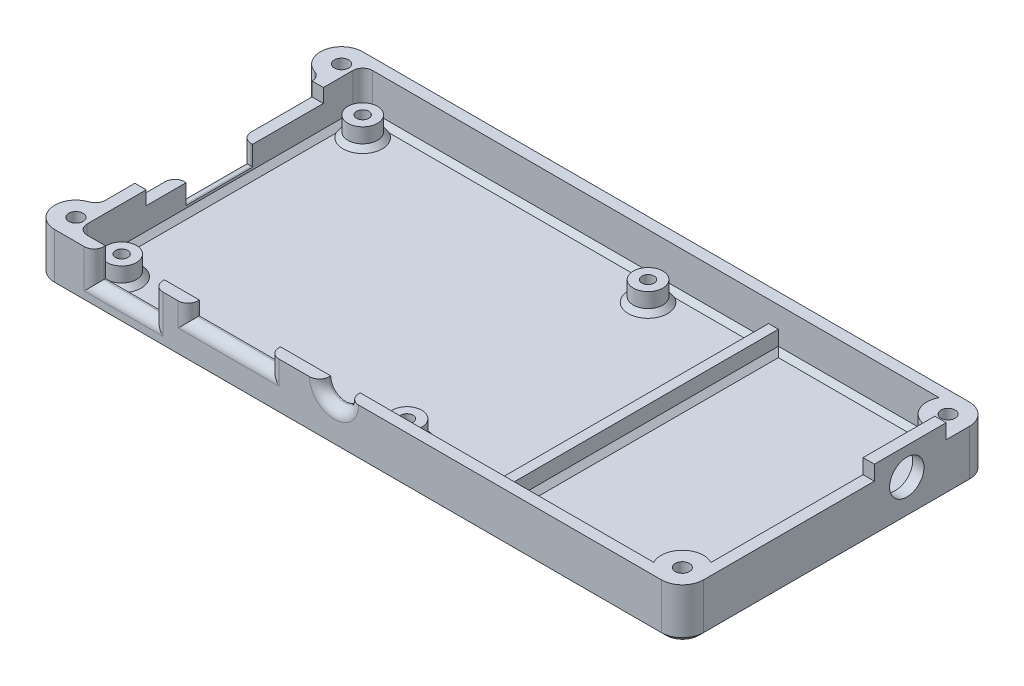
SolidWorks part; units mm, degrees
ref_plane "Front Plane" through (0, 0, 0) normal (0, 0, 1) x (1, 0, 0)
ref_plane "Top Plane" through (0, 0, 0) normal (0, 1, 0) x (1, 0, 0)
ref_plane "Right Plane" through (0, 0, 0) normal (1, 0, 0) x (0, 0, -1)
sketch "Sketch1" plane through (0, 0, 0) normal (0, 1, 0) x (1, 0, 0)
  line L0 (-71.5618, 3.106) -> (49.4382, 3.106) construction
  line L1 (-71.5618, 31.106) -> (49.4382, 31.106)
  line L2 (-71.5618, 31.106) -> (-71.5618, -24.894)
  line L3 (-71.5618, -24.894) -> (49.4382, -24.894)
  line L4 (49.4382, 31.106) -> (49.4382, -24.894)
  line L5 (-60.6618, -24.894) -> (-60.6618, -31.6828) construction
  line L6 (-68.0618, 27.606) -> (-10.0618, 27.606)
  line L7 (-68.0618, 27.606) -> (-68.0618, -21.394)
  line L8 (-68.0618, -21.394) -> (-10.0618, -21.394)
  line L9 (-10.0618, 27.606) -> (-10.0618, -21.394)
  line L10 (-39.5618, -24.894) -> (-39.5618, -31.6828) construction
  line L11 (-18.0618, -24.894) -> (-18.0618, -31.6828) construction
  line L12 (-65.4118, -26.5648) -> (-55.9118, -26.5648) construction
  line L13 (-48.0618, -26.5648) -> (-31.0618, -26.5648) construction
  line L14 (-22.0618, -26.5648) -> (-14.0618, -26.5648) construction
  line L15 (-72.5618, 9.606) -> (-72.5618, -3.394) construction
  line L16 (-71.5618, 3.106) -> (-72.5618, 3.106) construction
  dimension "D1" = 121
  dimension "D2" = 56
  dimension "D3" = 49
  dimension "D4" = 58
  dimension "D5" = 3.5
  dimension "D6" = 3.5
  dimension "D7" = 10.9
  dimension "D8" = 32
  dimension "D9" = 53.5
  dimension "D10" = 2
  dimension "D11" = 13
  dimension "D12" = 9.5
  dimension "D13" = 17
  dimension "D14" = 8
sketch "Sketch3" plane through (0, 0, 0) normal (0, 1, 0) x (1, 0, 0)
  line L4 (52.7382, 34.406) -> (-74.8618, 34.406)
  line L5 (-74.8618, 34.406) -> (-74.8618, -28.194)
  line L6 (-74.8618, -28.194) -> (52.7382, -28.194)
  line L7 (52.7382, -28.194) -> (52.7382, 34.406)
  line L8 (50.4382, 32.106) -> (-72.5618, 32.106)
  line L9 (50.4382, -25.894) -> (50.4382, 32.106)
  line L10 (-72.5618, -25.894) -> (50.4382, -25.894)
  line L11 (-72.5618, 32.106) -> (-72.5618, -25.894)
  line L12 (50.4382, 32.106) -> (-72.5618, 32.106)
  line L13 (50.4382, -25.894) -> (50.4382, 32.106)
  line L14 (-72.5618, -25.894) -> (50.4382, -25.894)
  line L15 (-72.5618, 32.106) -> (-72.5618, -25.894)
  line L16 (-11.0618, 3.106) -> (-11.0618, 34.406) construction
  line L17 (-71.5618, 3.106) -> (49.4382, 3.106) construction
  line L20 (-74.8618, 3.106) -> (52.7382, 3.106) construction
  line L25 (52.7382, -28.194) -> (52.7382, 34.406) construction
  line L26 (50.4382, -25.894) -> (50.4382, 32.106) construction
  dimension "D1" = 1
  dimension "D2" = 2.3
extrude "Boss-Extrude1" add sketch "Sketch3" along normal blind 10.3
sketch "Sketch5" plane through (0, 0, 0) normal (0, 1, 0) x (1, 0, 0)
  line L1 (-72.5618, 32.106) -> (50.4382, 32.106)
  line L2 (-72.5618, 32.106) -> (-72.5618, -25.894)
  line L3 (-72.5618, -25.894) -> (50.4382, -25.894)
  line L4 (50.4382, 32.106) -> (50.4382, -25.894)
extrude "Boss-Extrude2" add sketch "Sketch5" along normal blind 2
sketch "Sketch6" plane through (0, 2, 0) normal (0, 1, 0) x (1, 0, 0)
  circle A0 centre (-68.0618, 27.606) radius 3
  circle A1 centre (-68.0618, -21.394) radius 3
  circle A2 centre (-10.0618, -21.394) radius 3
  circle A3 centre (-10.0618, 27.606) radius 3
extrude "Boss-Extrude3" add sketch "Sketch6" along normal blind 4
hole_wizard "Ø2.5 (2.5) Diameter Hole1" positions "Sketch8" profile "Sketch9" hole size "Ø2.5" standard "ANSI Metric"
sketch "Sketch8" plane through (0, 6, 0) normal (0, 1, 0) x (1, 0, 0)
  point P0 (-68.0618, 27.606)
  point P3 (-10.0618, 27.606)
  point P6 (-10.0618, -21.394)
  point P9 (-68.0618, -21.394)
sketch "Sketch9" plane through (-68.0618, 6, -27.606) normal (1, 0, 0) x (0, 0, 1)
  line L0 (0, 0) -> (0, 8.7511)
  line L1 (0, 8.7511) -> (1.25, 8)
  line L2 (1.25, 8) -> (1.25, 0)
  line L5 (1.25, 0) -> (0, 0)
  line L10 (0, 8.7511) -> (-1.25, 8) construction
  line L11 (0, -6.35) -> (0, 107.95) construction
  dimension "Hole Dia." = 2.5
  dimension "Hole Depth" = 8
  dimension "Drill Angle" = 118
sketch "Sketch10" plane through (0, 2, 0) normal (0, 1, 0) x (1, 0, 0)
  line L0 (50.4382, 32.106) -> (-72.5618, 32.106) construction
  line L1 (9.9382, 32.106) -> (11.9382, 32.106)
  line L2 (9.9382, 32.106) -> (9.9382, -25.894)
  line L3 (9.9382, -25.894) -> (11.9382, -25.894)
  line L4 (11.9382, 32.106) -> (11.9382, -25.894)
  line L5 (-72.5618, -25.894) -> (50.4382, -25.894) construction
  line L6 (-10.0618, 27.606) -> (-10.0618, -21.394) construction
  dimension "D1" = 2
  dimension "D2" = 20
extrude "Boss-Extrude4" add sketch "Sketch10" along normal blind 4
sketch "Sketch11" plane through (0, 0, 28.194) normal (0, 0, 1) x (1, 0, 0)
  line L0 (-74.8618, 10.3) -> (-74.8618, 0) construction
  line L1 (-66.8618, 10.3) -> (-54.8618, 10.3)
  line L2 (-66.8618, 10.3) -> (-66.8618, 4.5)
  line L3 (-66.8618, 4.5) -> (-54.8618, 4.5)
  line L4 (-54.8618, 10.3) -> (-54.8618, 4.5)
  line L5 (-74.8618, 0) -> (52.7382, 0) construction
  line L6 (-60.8618, 10.3) -> (-60.6618, 0) construction
  line L7 (-65.4118, 0) -> (-55.9118, 0) construction
  line L9 (-47.778, 10.3) -> (-31.278, 10.3)
  line L10 (-47.778, 10.3) -> (-47.778, 7.5)
  line L11 (-47.778, 7.5) -> (-31.278, 7.5)
  line L12 (-31.278, 10.3) -> (-31.278, 7.5)
  line L13 (-68.0618, 0) -> (-10.0618, 0) construction
  line L14 (-39.5618, 0) -> (-39.528, 10.3) construction
  line L15 (-48.0618, 0) -> (-31.0618, 0) construction
  line L16 (-18.0618, 0) -> (-18.0618, 10.3) construction
  line L17 (-22.0618, 0) -> (-14.0618, 0) construction
  line L18 (-74.8618, 10.3) -> (52.7382, 10.3) construction
  circle A0 centre (-18.0618, 10.3) radius 3
  dimension "D5" = 6
  dimension "D1" = 4.5
  dimension "D2" = 12
  dimension "D3" = 7.5
  dimension "D4" = 16.5
  dimension "D6" = 8
extrude "Cut-Extrude1" cut sketch "Sketch11" against normal up to next
sketch "Sketch12" plane through (-74.8618, 0, 0) normal (-1, 0, 0) x (0, 0, 1)
  line L0 (-3.106, 0) -> (-3.106, 10.3) construction
  line L1 (-27.606, 0) -> (21.394, 0) construction
  line L2 (-34.406, 10.3) -> (28.194, 10.3) construction
  line L4 (-9.7329, 10.3) -> (3.7671, 10.3)
  line L5 (-9.7329, 10.3) -> (-9.7329, 3.5)
  line L6 (-9.7329, 3.5) -> (3.7671, 3.5)
  line L7 (3.7671, 10.3) -> (3.7671, 3.5)
  line L8 (-24.106, 10.3) -> (11.894, 10.3)
  line L9 (-24.106, 10.3) -> (-24.106, 7.5)
  line L10 (-24.106, 7.5) -> (11.894, 7.5)
  line L11 (11.894, 10.3) -> (11.894, 7.5)
  dimension "D1" = 13.5
  dimension "D2" = 3.5
  dimension "D3" = 7.5
  dimension "D4" = 36
extrude "Cut-Extrude2" cut sketch "Sketch12" against normal up to next contours L10 L11 L8 L9 | L7 L6 L5 L4
fillet "Fillet6" radius 2 1 edges at (50.4382, 6.15, -32.106)
fillet "Fillet8" radius 2 2 edges at (-72.5618, 6.15, 25.894) (-72.5618, 6.15, -32.106)
chamfer "Chamfer1" distance 1 angle 45 4 edges at (-68.0618, 2, 24.394) (-10.0618, 2, 24.394) (-10.0618, 2, -24.606) (-68.0618, 2, -24.606)
fillet "Fillet9" radius 2 9 edges at (-74.8618, 5.5, -9.7329) (-74.8618, 3.5, -2.9829) (-74.8618, 5.5, 3.7671) (-18.0618, 7.3, 28.194) (-31.278, 8.9, 28.194) (-47.778, 8.9, 28.194) (-39.528, 7.5, 28.194) (-54.8618, 7.4, 28.194) (-60.8618, 4.5, 28.194)
sketch "Sketch13" plane through (52.7382, 0, -61.1442) normal (1, 0, 0) x (0, 0, -1)
  line L1 (-26.7382, 10.3) -> (-26.7382, 0) construction
  circle A1 centre (-43.7382, 7.7223) radius 3.5
  dimension "D2" = 17
sketch "Sketch17" plane through (0, 0, 0) normal (0, 1, 0) x (1, 0, 0)
  line L0 (-74.8618, 34.406) -> (-74.8618, 24.106) construction
  line L1 (-74.8618, 34.406) -> (-74.8618, 25.806)
  line L2 (-74.8618, 25.806) -> (-74.659, 25.9406)
  line L3 (-74.8618, -19.594) -> (-74.8618, -28.194)
  line L4 (-74.8618, -28.194) -> (-74.659, -28.0594)
  arc A0 (-74.8618, -19.594) -> (-74.8618, -28.194) centre (-74.8618, -23.894) ccw
  arc A1 (-74.8618, 34.406) -> (-74.8618, 25.806) centre (-74.8618, 30.106) ccw
extrude "Boss-Extrude6" add sketch "Sketch17" along normal up to vertex (10.3 mm away) contours L1 A1 | L3 A0 region at (-76.6867, 0, -30.106) region at (-76.6867, 0, 23.894) up to point (-74.8618, 10.3, 28.194)
hole_wizard "Ø2.9 (2.9) Diameter Hole2" positions "Sketch19" profile "Sketch18" hole size "Ø2.9" standard "ANSI Metric" end condition up to next
sketch "Sketch19" plane through (0, 10.3, 0) normal (0, 1, 0) x (1, 0, 0)
  point P0 (-74.8618, 30.106)
sketch "Sketch18" plane through (-74.8618, 10.3, -30.106) normal (1, 0, 0) x (0, 0, 1)
  line L0 (0, 0) -> (0, 10.3)
  line L1 (0, 10.3) -> (1.45, 10.3)
  line L2 (1.45, 10.3) -> (1.45, 0)
  line L5 (1.45, 0) -> (0, 0)
  line L11 (0, -6.35) -> (0, 107.95) construction
  dimension "Thru Hole Dia." = 2.9
  dimension "Thru Hole Depth" = 10.3
hole_wizard "Ø2.9 (2.9) Diameter Hole1" positions "Sketch21" profile "Sketch20" hole size "Ø2.9" standard "ANSI Metric" end condition up to next
sketch "Sketch21" plane through (0, 10.3, 0) normal (0, 1, 0) x (1, 0, 0)
  point P0 (-74.8618, -23.894)
sketch "Sketch20" plane through (-74.8618, 10.3, 23.894) normal (1, 0, 0) x (0, 0, 1)
  line L0 (0, 0) -> (0, 10.3)
  line L1 (0, 10.3) -> (1.45, 10.3)
  line L2 (1.45, 10.3) -> (1.45, 0)
  line L5 (1.45, 0) -> (0, 0)
  line L11 (0, -6.35) -> (0, 107.95) construction
  dimension "Thru Hole Dia." = 2.9
  dimension "Thru Hole Depth" = 10.3
sketch "Sketch24" plane through (0, 2, 0) normal (0, 1, 0) x (1, 0, 0)
  line L0 (11.9382, 3.106) -> (61.5789, 3.106) construction
  line L1 (11.9382, -25.894) -> (11.9382, 32.106) construction
  circle A0 centre (48.4185, -23.894) radius 4.3
  circle A1 centre (48.4185, 30.106) radius 4.3
extrude "Boss-Extrude7" add sketch "Sketch24" along normal up to surface (8.3 mm away) up to face at (-74.8618, 10.3, 25.344)
hole_wizard "Ø2.9 (2.9) Diameter Hole5" positions "Sketch31" profile "Sketch30" hole size "Ø2.9" standard "ANSI Metric" end condition up to next
sketch "Sketch31" plane through (0, 10.3, 0) normal (0, 1, 0) x (1, 0, 0)
  point P0 (48.4185, -23.894)
sketch "Sketch30" plane through (48.4185, 10.3, 23.894) normal (1, 0, 0) x (0, 0, 1)
  line L0 (0, 0) -> (0, 10.3)
  line L1 (0, 10.3) -> (1.45, 10.3)
  line L2 (1.45, 10.3) -> (1.45, 0)
  line L5 (1.45, 0) -> (0, 0)
  line L11 (0, -6.35) -> (0, 107.95) construction
  dimension "Thru Hole Dia." = 2.9
  dimension "Thru Hole Depth" = 10.3
hole_wizard "Ø2.9 (2.9) Diameter Hole4" positions "Sketch28" profile "Sketch27" hole size "Ø2.9" standard "ANSI Metric" end condition up to next
sketch "Sketch28" plane through (0, 10.3, 0) normal (0, 1, 0) x (1, 0, 0)
  point P0 (48.4185, 30.106)
sketch "Sketch27" plane through (48.4185, 10.3, -30.106) normal (1, 0, 0) x (0, 0, 1)
  line L0 (0, 0) -> (0, 10.3)
  line L1 (0, 10.3) -> (1.45, 10.3)
  line L2 (1.45, 10.3) -> (1.45, 0)
  line L5 (1.45, 0) -> (0, 0)
  line L11 (0, -6.35) -> (0, 107.95) construction
  dimension "Thru Hole Dia." = 2.9
  dimension "Thru Hole Depth" = 10.3
fillet "Fillet10" radius 4.3 1 edges at (52.7382, 5.15, -34.406)
fillet "Fillet18" radius 2 2 edges at (-74.8618, 5.15, 19.594) (-74.8618, 5.15, -25.806)
chamfer "Chamfer3" distance 1 angle 45 9 edges at (51.4788, 0, -33.1466) (-13.2118, 0, -34.406) (52.7382, 0, -0.956) (-79.1058, 0, -30.7975) (-75.2385, 0, -25.3002) (-74.8618, 0, -3.106) (-75.2385, 0, 19.0883) (-79.1058, 0, 24.5855) (-11.0618, 0, 28.194)
fillet "Fillet19" radius 2 1 edges at (-66.8618, 6.4, 28.194)
fillet "Fillet20" radius 4.3 1 edges at (52.7382, 5.65, 28.194)
chamfer "Chamfer5" distance 1 angle 45 8 edges at (-72.5618, 2, -3.106) (-71.976, 2, 25.3082) (-71.976, 2, -31.5202) (-30.3118, 2, 25.894) (-30.3118, 2, -32.106) (9.9382, 2, -3.106) (11.9382, 2, -3.106) (28.2751, 2, -32.106)
chamfer "Chamfer6" distance 1 angle 45 1 edges at (50.4382, 2, -3.106)
sketch "Sketch29" plane through (0, 10.3, 0) normal (0, 1, 0) x (1, 0, 0)
  line L0 (50.4382, -20.0979) -> (50.4382, 26.3099) construction
  line L1 (50.4382, 25.406) -> (52.7382, 25.406)
  line L2 (50.4382, 25.406) -> (50.4382, 10.806)
  line L3 (50.4382, 10.806) -> (52.7382, 10.806)
  line L4 (52.7382, 25.406) -> (52.7382, 10.806)
  line L5 (52.7382, -23.894) -> (52.7382, 30.106) construction
  line L6 (48.4382, 34.406) -> (-74.8618, 34.406) construction
  line L7 (-13.0618, -28.194) -> (48.4382, -28.194) construction
  dimension "D1" = 9
  dimension "D2" = 39
extrude "Boss-Extrude8" add sketch "Sketch29" along normal blind 3
extrude "Cut-Extrude3" cut sketch "Sketch13" against normal up to next
sketch "Sketch32" plane through (0, 2, 0) normal (0, 1, 0) x (1, 0, 0)
  line L0 (12.9382, -25.894) -> (44.6119, -25.894) construction
  line L1 (15.4382, -15.694) -> (45.5382, -15.694)
  line L2 (15.4382, -15.694) -> (15.4382, -25.894)
  line L3 (15.4382, -25.894) -> (45.5382, -25.894)
  line L4 (45.5382, -15.694) -> (45.5382, -25.894)
  line L5 (-72.5618, -23.894) -> (-72.5618, 30.106) construction
  dimension "D1" = 10.2
  dimension "D2" = 30.1
  dimension "D3" = 88
sketch "Sketch34" plane through (0, 0, 28.194) normal (0, 0, 1) x (1, 0, 0)
  line L0 (17.9748, 7.7443) -> (19.8911, 2.8029) construction
  line L1 (19.1402, 8.1963) -> (21.0565, 3.2549)
  line L2 (16.8093, 7.2924) -> (18.7256, 2.3509)
  line L3 (22.9748, 7.7443) -> (24.8911, 2.8029) construction
  line L4 (24.1402, 8.1963) -> (26.0565, 3.2549)
  line L5 (21.8093, 7.2924) -> (23.7256, 2.3509)
  line L6 (27.9748, 7.7443) -> (29.8911, 2.8029) construction
  line L7 (29.1402, 8.1963) -> (31.0565, 3.2549)
  line L8 (26.8093, 7.2924) -> (28.7256, 2.3509)
  line L9 (32.9748, 7.7443) -> (34.8911, 2.8029) construction
  line L10 (34.1402, 8.1963) -> (36.0565, 3.2549)
  line L11 (31.8093, 7.2924) -> (33.7256, 2.3509)
  line L12 (37.9748, 7.7443) -> (39.8911, 2.8029) construction
  line L13 (39.1402, 8.1963) -> (41.0565, 3.2549)
  line L14 (36.8093, 7.2924) -> (38.7256, 2.3509)
  arc A0 (19.1402, 8.1963) -> (16.8093, 7.2924) centre (17.9748, 7.7443) ccw
  arc A1 (18.7256, 2.3509) -> (21.0565, 3.2549) centre (19.8911, 2.8029) ccw
  arc A2 (24.1402, 8.1963) -> (21.8093, 7.2924) centre (22.9748, 7.7443) ccw
  arc A3 (23.7256, 2.3509) -> (26.0565, 3.2549) centre (24.8911, 2.8029) ccw
  arc A4 (29.1402, 8.1963) -> (26.8093, 7.2924) centre (27.9748, 7.7443) ccw
  arc A5 (28.7256, 2.3509) -> (31.0565, 3.2549) centre (29.8911, 2.8029) ccw
  arc A6 (34.1402, 8.1963) -> (31.8093, 7.2924) centre (32.9748, 7.7443) ccw
  arc A7 (33.7256, 2.3509) -> (36.0565, 3.2549) centre (34.8911, 2.8029) ccw
  arc A8 (39.1402, 8.1963) -> (36.8093, 7.2924) centre (37.9748, 7.7443) ccw
  arc A9 (38.7256, 2.3509) -> (41.0565, 3.2549) centre (39.8911, 2.8029) ccw
  point P2 (18.9329, 5.2736)
  point P9 (23.9329, 5.2736)
  point P16 (28.9329, 5.2736)
  point P23 (33.9329, 5.2736)
  point P30 (38.9329, 5.2736)
chamfer "Chamfer7" distance 1 angle 45 1 edges at (51.4788, 0, 26.9346)
